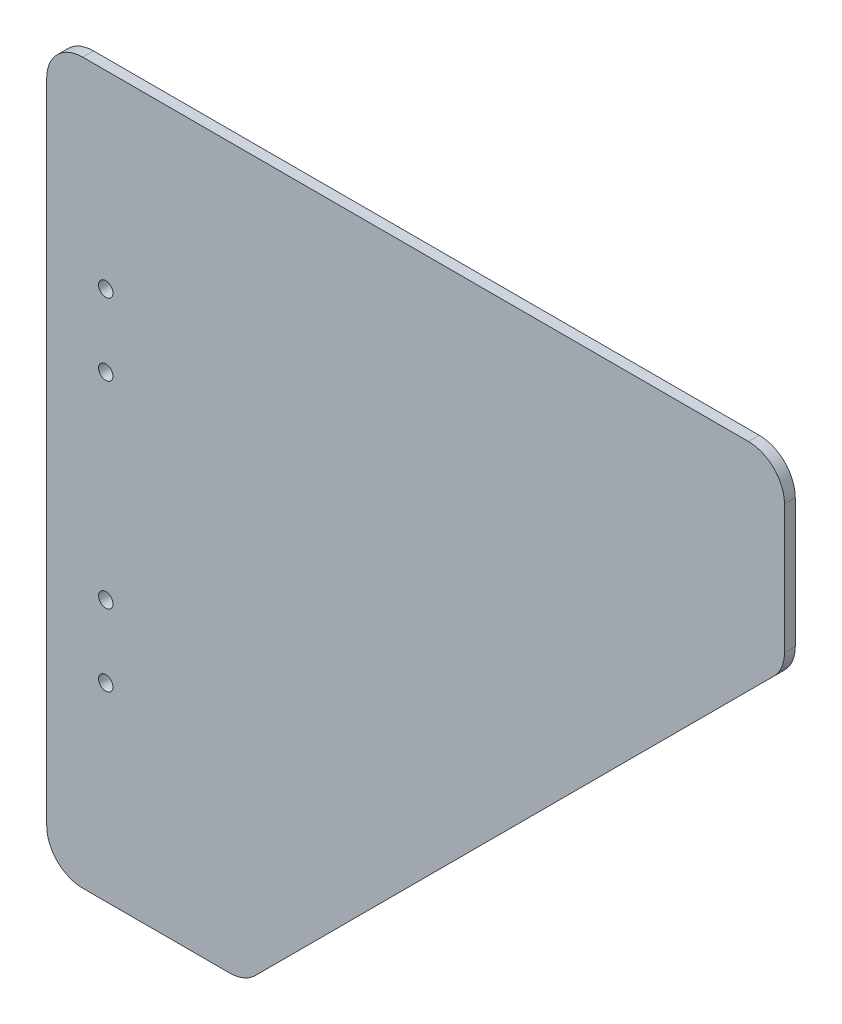
SolidWorks part; units mm, degrees
ref_plane "Piano frontale" through (0, 0, 0) normal (0, 0, 1) x (1, 0, 0)
ref_plane "Piano superiore" through (0, 0, 0) normal (0, 1, 0) x (1, 0, 0)
ref_plane "Piano destro" through (0, 0, 0) normal (1, 0, 0) x (0, 0, -1)
sketch "Schizzo1" plane through (0, 0, 0) normal (0, 0, 1) x (1, 0, 0)
  line L0 (0, 10) -> (0, 190)
  line L1 (10, 200) -> (195, 200)
  line L2 (205, 190) -> (205, 154.1421)
  line L3 (202.0711, 147.0711) -> (57.9289, 2.9289)
  line L4 (50.8579, 0) -> (10, 0)
  arc A0 (57.9289, 2.9289) -> (50.8579, 0) centre (50.8579, 10) cw
  arc A1 (205, 154.1421) -> (202.0711, 147.0711) centre (195, 154.1421) cw
  arc A2 (195, 200) -> (205, 190) centre (195, 190) cw
  arc A3 (10, 200) -> (0, 190) centre (10, 190) ccw
  arc A4 (0, 10) -> (10, 0) centre (10, 10) ccw
  point P6 (205, 172.0711)
  point P11 (205, 150)
  point P14 (205, 200)
  point P19 (0, 0)
  dimension "D5" = 10
  dimension "D6" = 10
  dimension "D1" = 45
  dimension "D2" = 50
  dimension "D3" = 200
  dimension "D4" = 205
extrude "Estrusione-Estrusione1" add sketch "Schizzo1" along normal blind 3
sketch "Schizzo2" plane through (0, 0, 3) normal (0, 0, 1) x (1, 0, 0)
  line L0 (0, 190) -> (0, 10) construction
  line L1 (10, 0) -> (50.8579, 0) construction
  line L2 (0, 100) -> (155, 100) construction
  line L3 (57.9289, 2.9289) -> (202.0711, 147.0711) construction
  circle A0 centre (16.4, 52.6) radius 2
  circle A1 centre (16.4, 72.6) radius 2
  circle A2 centre (16.4, 127.4) radius 2
  circle A3 centre (16.4, 147.4) radius 2
  dimension "D1" = 4
  dimension "D2" = 4
  dimension "D5" = 52.6
  dimension "D3" = 20
  dimension "D4" = 16.4
extrude "Taglio-Estrusione1" cut sketch "Schizzo2" against normal blind 10
